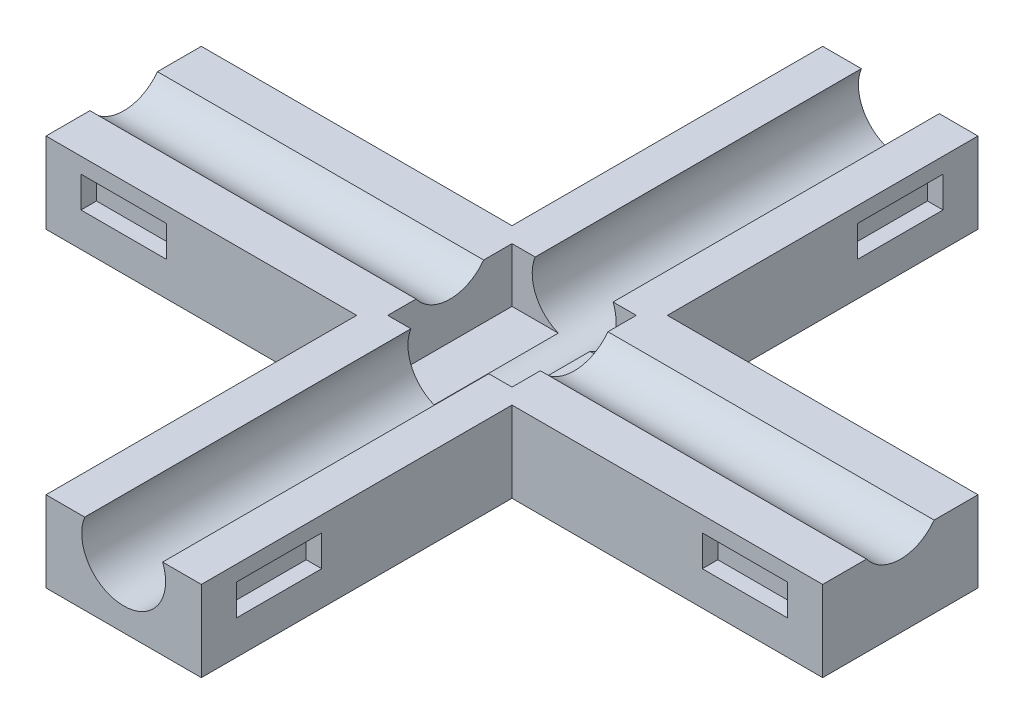
SolidWorks part; units mm, degrees
ref_plane "Front Plane" through (0, 0, 0) normal (0, 0, 1) x (1, 0, 0)
ref_plane "Top Plane" through (0, 0, 0) normal (0, 1, 0) x (1, 0, 0)
ref_plane "Right Plane" through (0, 0, 0) normal (1, 0, 0) x (0, 0, -1)
ref_plane "Plane1" through (0, 1, 0) normal (0, 1, 0) x (1, 0, 0)
ref_axis "Axis1" through (0, 4.725, 0) along (0, -1, 0)
sketch "Sketch3" plane through (0, 0, 0) normal (0, 1, 0) x (1, 0, 0)
  line L1 (5, 5) -> (25, 5)
  line L2 (-5, 25) -> (5, 25)
  line L3 (-5, 25) -> (-5, 5)
  line L5 (5, 25) -> (5, 5)
  line L7 (5, -5) -> (25, -5)
  line L8 (25, 5) -> (25, -5)
  line L10 (5, -5) -> (5, -25)
  line L11 (5, -25) -> (-5, -25)
  line L12 (-5, -5) -> (-5, -25)
  line L13 (-5, -5) -> (-25, -5)
  line L15 (-5, 5) -> (-25, 5)
  line L16 (-25, -5) -> (-25, 5)
  point P11 (0, 25)
  point P15 (-25, 0)
  dimension "D1" = 10
  dimension "D3" = 20
extrude "Boss-Extrude5" add sketch "Sketch3" along normal blind 5.2
sketch "Sketch4" plane through (0, 0, 25) normal (0, 0, 1) x (1, 0, 0)
  line L1 (-5, 0) -> (5, 0) construction
  line L2 (-5, 5.2) -> (5, 5.2) construction
  circle A0 centre (0, 4.2) radius 2.7
  point P5 (0, 0)
  dimension "D1" = 5.4
  dimension "D2" = 1
extrude "Cut-Extrude1" cut sketch "Sketch4" against normal up to next
sketch "Sketch5" plane through (25, 0, 0) normal (1, 0, 0) x (0, 0, -1)
  line L0 (-5, 0) -> (5, 0) construction
  line L1 (-5, 5.2) -> (5, 5.2) construction
  circle A0 centre (0, 6.8) radius 2.7
  point P4 (0, 0)
  dimension "D1" = 5.4
  dimension "D2" = 1.6
extrude "Cut-Extrude2" cut sketch "Sketch5" against normal through all
sketch "Sketch6" plane through (0, 5.2, 0) normal (0, 1, 0) x (1, 0, 0)
  line L1 (4, 4) -> (-4, 4)
  line L2 (4, 4) -> (4, -4)
  line L3 (4, -4) -> (-4, -4)
  line L4 (-4, 4) -> (-4, -4)
  line L5 (4, 4) -> (-4, -4) construction
  line L6 (4, -4) -> (-4, 4) construction
  point P0 (0, 0)
  dimension "D1" = 8
  dimension "D2" = 8
extrude "Cut-Extrude3" cut sketch "Sketch6" against normal blind 3.5
sketch "Sketch7" plane through (0, 0, 5) normal (0, 0, 1) x (1, 0, 0)
  line L0 (25, 5.2) -> (25, 0) construction
  line L1 (17.25, 2.2) -> (22.75, 2.2)
  line L2 (17.25, 2.2) -> (17.25, 4.2)
  line L3 (17.25, 4.2) -> (22.75, 4.2)
  line L4 (22.75, 2.2) -> (22.75, 4.2)
  line L5 (17.25, 2.2) -> (22.75, 4.2) construction
  line L6 (17.25, 4.2) -> (22.75, 2.2) construction
  line L7 (5, 5.2) -> (25, 5.2) construction
  point P0 (20, 3.2)
  dimension "D1" = 5
  dimension "D2" = 5.5
  dimension "D3" = 2
  dimension "D4" = 1
extrude "Cut-Extrude4" cut sketch "Sketch7" against normal blind 1
mirror "Mirror1" about plane through (0, 0, 0) normal (0, 0, 1) of "Cut-Extrude4"
pattern_circular "CirPattern1" count 4 over 360 about axis through (0, 4.725, 0) along (0, -1, 0) of "Mirror1"
sketch "Sketch8" plane through (0, 0, 0) normal (0, 1, 0) x (1, 0, 0)
  line L1 (-5, 5) -> (5, 5)
  line L2 (-5, 5) -> (-5, -5)
  line L3 (-5, -5) -> (5, -5)
  line L4 (5, 5) -> (5, -5)
  line L5 (-5, 5) -> (5, -5) construction
  line L6 (-5, -5) -> (5, 5) construction
  point P0 (0, 0)
extrude "Boss-Extrude6" [suppressed] add sketch "Sketch8" along normal blind 10 separate body
other "Intersect1" [suppressed]
